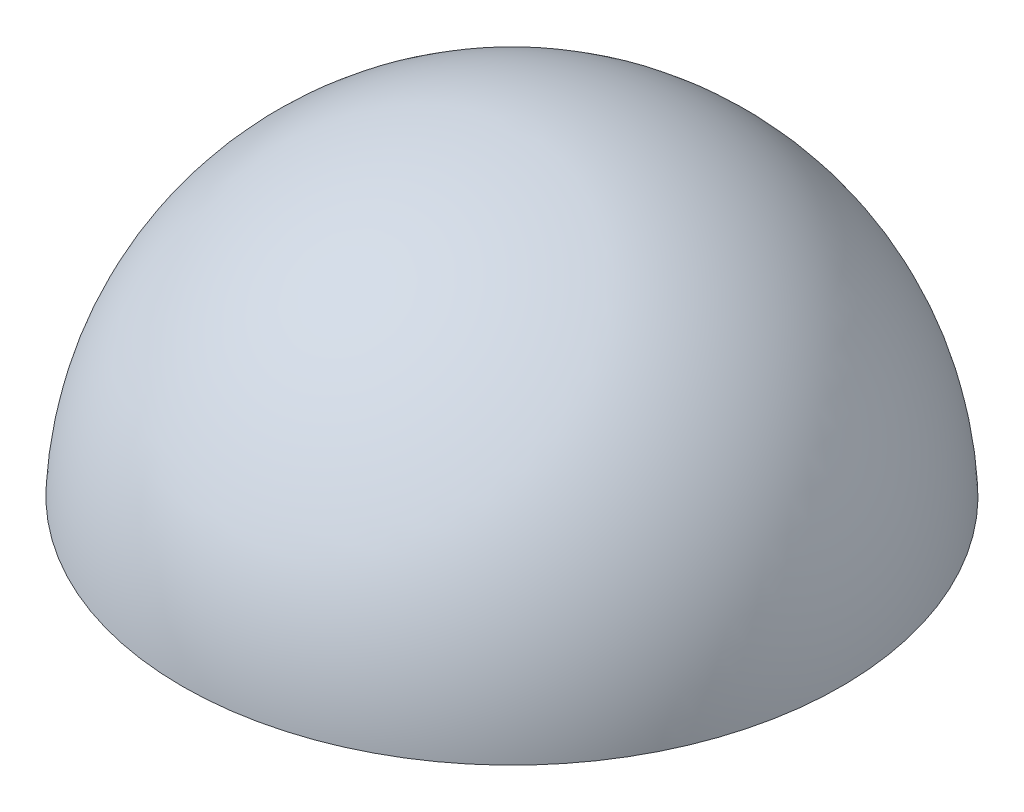
SolidWorks part; units mm, degrees
ref_plane "Front Plane" through (0, 0, 0) normal (0, 0, 1) x (1, 0, 0)
ref_plane "Top Plane" through (0, 0, 0) normal (0, 1, 0) x (1, 0, 0)
ref_plane "Right Plane" through (0, 0, 0) normal (1, 0, 0) x (0, 0, -1)
sketch "Sketch1" plane through (0, 0, 0) normal (0, 1, 0) x (1, 0, 0)
  line L0 (0, -44.45) -> (0, 44.45)
  arc A0 (0, 44.45) -> (0, -44.45) centre (0, 0) ccw
  arc A1 (0, 42.45) -> (0, -42.45) centre (0, 0) ccw
  circle A3 centre (0, 0) radius 44.45 construction
  circle A4 centre (0, 0) radius 42.45 construction
  point P1 (42.45, 0)
  point P6 (42.5077, 12.9959)
  dimension "D1" = 88.9
  dimension "D2" = 2
revolve "Revolve1" add sketch "Sketch1" angle 180 about L0 region at (-43.4561, 0, 0)
sketch "Sketch2" plane through (0, 0, 0) normal (0, 1, 0) x (1, 0, 0)
  circle A0 centre (0, 0) radius 44.45
extrude "Cut-Extrude1" cut sketch "Sketch2" along normal blind 2
sketch "30deg" plane through (0, 0, 0) normal (1, 0, 0) x (0, 0, -1)
  line L0 (0, 0) -> (38.4948, 22.225) construction
  line L1 (0, 0) -> (44.45, 0) construction
  line L7 (0, 0) -> (22.225, 38.4948) construction
  line L8 (0, 0) -> (44.45, 0) construction
  line L10 (0, 0) -> (38.4948, 22.225) construction
  line L25 (0, 0) -> (0, 49000) construction
  dimension "D2" = 3
  dimension "D3" = 30
  dimension "D1" = 44.45
sketch "Sketch4" plane through (0, 0, 0) normal (0, 1, 0) x (1, 0, 0)
  line L0 (0, 0) -> (0, 43.45)
  line L1 (0.5, 44.45) -> (-0.5, 44.45)
  line L2 (-0.5, 43.45) -> (0.5, 43.45)
  line L3 (-0.5, 43.45) -> (-0.5, 44.45)
  line L4 (0.5, 43.45) -> (0.5, 44.45)
  line L5 (0, 0) -> (21.725, 37.6288)
  line L6 (21.292, 37.8788) -> (21.792, 38.7448)
  line L7 (21.292, 37.8788) -> (22.158, 37.3788)
  line L8 (22.158, 37.3788) -> (22.658, 38.2448)
  line L9 (22.658, 38.2448) -> (21.792, 38.7448)
  line L10 (0, 0) -> (37.6288, 21.725)
  line L11 (37.3788, 22.158) -> (38.2448, 22.658)
  line L12 (37.3788, 22.158) -> (37.8788, 21.292)
  line L13 (37.8788, 21.292) -> (38.7448, 21.792)
  line L14 (38.7448, 21.792) -> (38.2448, 22.658)
  line L15 (0, 0) -> (43.45, 0)
  line L16 (43.45, 0.5) -> (44.45, 0.5)
  line L17 (43.45, 0.5) -> (43.45, -0.5)
  line L18 (43.45, -0.5) -> (44.45, -0.5)
  line L19 (44.45, -0.5) -> (44.45, 0.5)
  line L20 (0, 0) -> (37.6288, -21.725)
  line L21 (37.8788, -21.292) -> (38.7448, -21.792)
  line L22 (37.8788, -21.292) -> (37.3788, -22.158)
  line L23 (37.3788, -22.158) -> (38.2448, -22.658)
  line L24 (38.2448, -22.658) -> (38.7448, -21.792)
  line L25 (0, 0) -> (21.725, -37.6288)
  line L26 (22.158, -37.3788) -> (22.658, -38.2448)
  line L27 (22.158, -37.3788) -> (21.292, -37.8788)
  line L28 (21.292, -37.8788) -> (21.792, -38.7448)
  line L29 (21.792, -38.7448) -> (22.658, -38.2448)
  line L30 (0, 0) -> (0, -43.45)
  line L31 (0.5, -43.45) -> (0.5, -44.45)
  line L32 (0.5, -43.45) -> (-0.5, -43.45)
  line L33 (-0.5, -43.45) -> (-0.5, -44.45)
  line L34 (-0.5, -44.45) -> (0.5, -44.45)
  line L35 (0, 0) -> (-21.725, -37.6288)
  line L36 (-21.292, -37.8788) -> (-21.792, -38.7448)
  line L37 (-21.292, -37.8788) -> (-22.158, -37.3788)
  line L38 (-22.158, -37.3788) -> (-22.658, -38.2448)
  line L39 (-22.658, -38.2448) -> (-21.792, -38.7448)
  line L40 (0, 0) -> (-37.6288, -21.725)
  line L41 (-37.3788, -22.158) -> (-38.2448, -22.658)
  line L42 (-37.3788, -22.158) -> (-37.8788, -21.292)
  line L43 (-37.8788, -21.292) -> (-38.7448, -21.792)
  line L44 (-38.7448, -21.792) -> (-38.2448, -22.658)
  line L45 (0, 0) -> (-43.45, 0)
  line L46 (-43.45, -0.5) -> (-44.45, -0.5)
  line L47 (-43.45, -0.5) -> (-43.45, 0.5)
  line L48 (-43.45, 0.5) -> (-44.45, 0.5)
  line L49 (-44.45, 0.5) -> (-44.45, -0.5)
  line L50 (0, 0) -> (-37.6288, 21.725)
  line L51 (-37.8788, 21.292) -> (-38.7448, 21.792)
  line L52 (-37.8788, 21.292) -> (-37.3788, 22.158)
  line L53 (-37.3788, 22.158) -> (-38.2448, 22.658)
  line L54 (-38.2448, 22.658) -> (-38.7448, 21.792)
  line L55 (0, 0) -> (-21.725, 37.6288)
  line L56 (-22.158, 37.3788) -> (-22.658, 38.2448)
  line L57 (-22.158, 37.3788) -> (-21.292, 37.8788)
  line L58 (-21.292, 37.8788) -> (-21.792, 38.7448)
  line L59 (-21.792, 38.7448) -> (-22.658, 38.2448)
  line L60 (0, 0) -> (0, 43.45) construction
  line L61 (0, 0) -> (21.725, 37.6288) construction
  circle A0 centre (0, 0) radius 44.45 construction
  point P7 (0, 44.45)
  point P10 (0, 43.45)
  dimension "D1" = 88.9
  dimension "D2" = 1
  dimension "D3" = 1
  dimension "D5" = 30
  dimension "D4" = 12
ref_plane "Plane1" through (0, 44.45, 0) normal (0, 1, 0) x (1, 0, 0)
sketch "Sketch5" plane through (0, 44.45, 0) normal (0, 1, 0) x (1, 0, 0)
  circle A0 centre (0, 0) radius 0.5
  dimension "D1" = 1
sketch "Sketch6" plane through (0, 0, 0) normal (0, 0, 1) x (1, 0, 0)
  line L0 (44.45, 0) -> (-44.45, 0) construction
  line L1 (-43.45, 0) -> (-44.45, 0) construction
  arc A0 (-44.45, 0) -> (0, 44.45) centre (0, 0) cw
ref_axis "Axis1" through (0, 117.8347, 0) along (0, -1, 0)
sketch "Sketch7" plane through (0, 44.45, 0) normal (0, 1, 0) x (1, 0, 0)
  line L0 (0, 0) -> (0, 88.8986) construction
  line L4 (-0.5, 38.9916) -> (-0.5, 88.8986)
  line L5 (0.5, 38.9916) -> (0.5, 88.8986)
  line L7 (-0.5, 22.7195) -> (-0.5, 37.9915)
  line L9 (0.5, 22.7195) -> (0.5, 37.9915)
  line L10 (0, 0) -> (44.4493, 76.9884) construction
  line L11 (19.0628, 34.0177) -> (44.0163, 77.2384)
  line L12 (19.9288, 33.5177) -> (44.8823, 76.7384)
  line L13 (10.9267, 19.9257) -> (18.5628, 33.1516)
  line L14 (11.7928, 19.4257) -> (19.4288, 32.6516)
  line L17 (0, 0) -> (76.9884, 44.4493) construction
  line L18 (33.5177, 19.9288) -> (76.7384, 44.8823)
  line L19 (34.0177, 19.0628) -> (77.2384, 44.0163)
  line L20 (19.4257, 11.7928) -> (32.6516, 19.4288)
  line L21 (19.9257, 10.9267) -> (33.1516, 18.5628)
  line L24 (0, 0) -> (88.8986, 0) construction
  line L25 (38.9916, 0.5) -> (88.8986, 0.5)
  line L26 (38.9916, -0.5) -> (88.8986, -0.5)
  line L27 (22.7195, 0.5) -> (37.9915, 0.5)
  line L28 (22.7195, -0.5) -> (37.9915, -0.5)
  line L31 (0, 0) -> (76.9884, -44.4493) construction
  line L32 (34.0177, -19.0628) -> (77.2384, -44.0163)
  line L33 (33.5177, -19.9288) -> (76.7384, -44.8823)
  line L34 (19.9257, -10.9267) -> (33.1516, -18.5628)
  line L35 (19.4257, -11.7928) -> (32.6516, -19.4288)
  line L38 (0, 0) -> (44.4493, -76.9884) construction
  line L39 (19.9288, -33.5177) -> (44.8823, -76.7384)
  line L40 (19.0628, -34.0177) -> (44.0163, -77.2384)
  line L41 (11.7928, -19.4257) -> (19.4288, -32.6516)
  line L42 (10.9267, -19.9257) -> (18.5628, -33.1516)
  line L45 (0, 0) -> (0, -88.8986) construction
  line L46 (0.5, -38.9916) -> (0.5, -88.8986)
  line L47 (-0.5, -38.9916) -> (-0.5, -88.8986)
  line L48 (0.5, -22.7195) -> (0.5, -37.9915)
  line L49 (-0.5, -22.7195) -> (-0.5, -37.9915)
  line L52 (0, 0) -> (-44.4493, -76.9884) construction
  line L53 (-19.0628, -34.0177) -> (-44.0163, -77.2384)
  line L54 (-19.9288, -33.5177) -> (-44.8823, -76.7384)
  line L55 (-10.9267, -19.9257) -> (-18.5628, -33.1516)
  line L56 (-11.7928, -19.4257) -> (-19.4288, -32.6516)
  line L59 (0, 0) -> (-76.9884, -44.4493) construction
  line L60 (-33.5177, -19.9288) -> (-76.7384, -44.8823)
  line L61 (-34.0177, -19.0628) -> (-77.2384, -44.0163)
  line L62 (-19.4257, -11.7928) -> (-32.6516, -19.4288)
  line L63 (-19.9257, -10.9267) -> (-33.1516, -18.5628)
  line L66 (0, 0) -> (-88.8986, 0) construction
  line L67 (-38.9916, -0.5) -> (-88.8986, -0.5)
  line L68 (-38.9916, 0.5) -> (-88.8986, 0.5)
  line L69 (-22.7195, -0.5) -> (-37.9915, -0.5)
  line L70 (-22.7195, 0.5) -> (-37.9915, 0.5)
  line L73 (0, 0) -> (-76.9884, 44.4493) construction
  line L74 (-34.0177, 19.0628) -> (-77.2384, 44.0163)
  line L75 (-33.5177, 19.9288) -> (-76.7384, 44.8823)
  line L76 (-19.9257, 10.9267) -> (-33.1516, 18.5628)
  line L77 (-19.4257, 11.7928) -> (-32.6516, 19.4288)
  line L80 (0, 0) -> (-44.4493, 76.9884) construction
  line L81 (-19.9288, 33.5177) -> (-44.8823, 76.7384)
  line L82 (-19.0628, 34.0177) -> (-44.0163, 77.2384)
  line L83 (-11.7928, 19.4257) -> (-19.4288, 32.6516)
  line L84 (-10.9267, 19.9257) -> (-18.5628, 33.1516)
  line L87 (0, 0) -> (0.5, 0) construction
  line L89 (-0.5, 1.866) -> (-0.5, 21.7192)
  line L90 (-0.5, 1.866) -> (-10.4266, 19.0594)
  line L91 (0.5, 1.866) -> (10.4266, 19.0594)
  line L92 (0.5, 1.866) -> (0.5, 21.7192)
  line L93 (1.366, 1.366) -> (18.5594, 11.2926)
  line L94 (1.366, 1.366) -> (11.2926, 18.5594)
  line L95 (1.866, 0.5) -> (21.7192, 0.5)
  line L96 (1.866, 0.5) -> (19.0594, 10.4266)
  line L97 (1.866, -0.5) -> (19.0594, -10.4266)
  line L98 (1.866, -0.5) -> (21.7192, -0.5)
  line L99 (1.366, -1.366) -> (11.2926, -18.5594)
  line L100 (1.366, -1.366) -> (18.5594, -11.2926)
  line L101 (0.5, -1.866) -> (0.5, -21.7192)
  line L102 (0.5, -1.866) -> (10.4266, -19.0594)
  line L103 (-0.5, -1.866) -> (-10.4266, -19.0594)
  line L104 (-0.5, -1.866) -> (-0.5, -21.7192)
  line L105 (-1.366, -1.366) -> (-11.2926, -18.5594)
  line L106 (-1.366, -1.366) -> (-18.5594, -11.2926)
  line L107 (-1.866, -0.5) -> (-21.7192, -0.5)
  line L108 (-1.866, -0.5) -> (-19.0594, -10.4266)
  line L109 (-1.866, 0.5) -> (-19.0594, 10.4266)
  line L110 (-1.866, 0.5) -> (-21.7192, 0.5)
  line L111 (-1.366, 1.366) -> (-11.2926, 18.5594)
  line L112 (-1.366, 1.366) -> (-18.5594, 11.2926)
  circle A0 centre (0, 0) radius 22.225 construction
  circle A1 centre (0, 0) radius 38.4948 construction
  arc A2 (-0.5, 38.9916) -> (-19.0628, 34.0177) centre (0, 0) ccw
  arc A3 (-0.5, 22.7195) -> (-10.9267, 19.9257) centre (0, 0) ccw
  arc A4 (-0.5, 37.9915) -> (-18.5628, 33.1516) centre (0, 0) ccw
  arc A5 (-0.5, 21.7192) -> (-10.4266, 19.0594) centre (0, 0) ccw
  arc A6 (0.5, 88.8986) -> (-0.5, 88.8986) centre (0, 0) ccw
  circle A9 centre (0, 0) radius 88.9 construction
  circle A10 centre (0, 0) radius 38.9948 construction
  circle A11 centre (0, 0) radius 37.9948 construction
  circle A13 centre (0, 0) radius 21.725 construction
  circle A14 centre (0, 0) radius 22.725 construction
  arc A15 (44.8823, 76.7384) -> (44.0163, 77.2384) centre (0, 0) ccw
  arc A16 (77.2384, 44.0163) -> (76.7384, 44.8823) centre (0, 0) ccw
  arc A17 (88.8986, -0.5) -> (88.8986, 0.5) centre (0, 0) ccw
  arc A18 (76.7384, -44.8823) -> (77.2384, -44.0163) centre (0, 0) ccw
  arc A19 (44.0163, -77.2384) -> (44.8823, -76.7384) centre (0, 0) ccw
  arc A20 (-0.5, -88.8986) -> (0.5, -88.8986) centre (0, 0) ccw
  arc A21 (-44.8823, -76.7384) -> (-44.0163, -77.2384) centre (0, 0) ccw
  arc A22 (-77.2384, -44.0163) -> (-76.7384, -44.8823) centre (0, 0) ccw
  arc A23 (-88.8986, 0.5) -> (-88.8986, -0.5) centre (0, 0) ccw
  arc A24 (-76.7384, 44.8823) -> (-77.2384, 44.0163) centre (0, 0) ccw
  arc A25 (-44.0163, 77.2384) -> (-44.8823, 76.7384) centre (0, 0) ccw
  arc A26 (-34.0177, 19.0628) -> (-38.9916, 0.5) centre (0, 0) ccw
  arc A27 (-33.1516, 18.5628) -> (-37.9915, 0.5) centre (0, 0) ccw
  arc A28 (-19.9288, 33.5177) -> (-33.5177, 19.9288) centre (0, 0) ccw
  arc A29 (-19.4288, 32.6516) -> (-32.6516, 19.4288) centre (0, 0) ccw
  arc A30 (19.0628, 34.0177) -> (0.5, 38.9916) centre (0, 0) ccw
  arc A31 (18.5628, 33.1516) -> (0.5, 37.9915) centre (0, 0) ccw
  arc A32 (32.6516, 19.4288) -> (19.4288, 32.6516) centre (0, 0) ccw
  arc A33 (33.5177, 19.9288) -> (19.9288, 33.5177) centre (0, 0) ccw
  arc A34 (37.9915, 0.5) -> (33.1516, 18.5628) centre (0, 0) ccw
  arc A35 (38.9916, 0.5) -> (34.0177, 19.0628) centre (0, 0) ccw
  arc A36 (33.1516, -18.5628) -> (37.9915, -0.5) centre (0, 0) ccw
  arc A37 (34.0177, -19.0628) -> (38.9916, -0.5) centre (0, 0) ccw
  arc A38 (19.4288, -32.6516) -> (32.6516, -19.4288) centre (0, 0) ccw
  arc A39 (19.9288, -33.5177) -> (33.5177, -19.9288) centre (0, 0) ccw
  arc A40 (0.5, -37.9915) -> (18.5628, -33.1516) centre (0, 0) ccw
  arc A41 (0.5, -38.9916) -> (19.0628, -34.0177) centre (0, 0) ccw
  arc A42 (-18.5628, -33.1516) -> (-0.5, -37.9915) centre (0, 0) ccw
  arc A43 (-19.0628, -34.0177) -> (-0.5, -38.9916) centre (0, 0) ccw
  arc A44 (-33.5177, -19.9288) -> (-19.9288, -33.5177) centre (0, 0) ccw
  arc A45 (-32.6516, -19.4288) -> (-19.4288, -32.6516) centre (0, 0) ccw
  arc A46 (-38.9916, -0.5) -> (-34.0177, -19.0628) centre (0, 0) ccw
  arc A47 (-37.9915, -0.5) -> (-33.1516, -18.5628) centre (0, 0) ccw
  arc A48 (-11.7928, 19.4257) -> (-19.4257, 11.7928) centre (0, 0) ccw
  arc A49 (-11.2926, 18.5594) -> (-18.5594, 11.2926) centre (0, 0) ccw
  arc A50 (-19.9257, 10.9267) -> (-22.7195, 0.5) centre (0, 0) ccw
  arc A51 (-19.0594, 10.4266) -> (-21.7192, 0.5) centre (0, 0) ccw
  arc A52 (-21.7192, -0.5) -> (-19.0594, -10.4266) centre (0, 0) ccw
  arc A53 (-22.7195, -0.5) -> (-19.9257, -10.9267) centre (0, 0) ccw
  arc A54 (10.4266, 19.0594) -> (0.5, 21.7192) centre (0, 0) ccw
  arc A55 (10.9267, 19.9257) -> (0.5, 22.7195) centre (0, 0) ccw
  arc A56 (18.5594, 11.2926) -> (11.2926, 18.5594) centre (0, 0) ccw
  arc A57 (19.4257, 11.7928) -> (11.7928, 19.4257) centre (0, 0) ccw
  arc A58 (21.7192, 0.5) -> (19.0594, 10.4266) centre (0, 0) ccw
  arc A59 (22.7195, 0.5) -> (19.9257, 10.9267) centre (0, 0) ccw
  arc A60 (19.9257, -10.9267) -> (22.7195, -0.5) centre (0, 0) ccw
  arc A61 (19.0594, -10.4266) -> (21.7192, -0.5) centre (0, 0) ccw
  arc A62 (11.2926, -18.5594) -> (18.5594, -11.2926) centre (0, 0) ccw
  arc A63 (11.7928, -19.4257) -> (19.4257, -11.7928) centre (0, 0) ccw
  arc A64 (0.5, -22.7195) -> (10.9267, -19.9257) centre (0, 0) ccw
  arc A65 (0.5, -21.7192) -> (10.4266, -19.0594) centre (0, 0) ccw
  arc A66 (-10.4266, -19.0594) -> (-0.5, -21.7192) centre (0, 0) ccw
  arc A67 (-10.9267, -19.9257) -> (-0.5, -22.7195) centre (0, 0) ccw
  arc A68 (-19.4257, -11.7928) -> (-11.7928, -19.4257) centre (0, 0) ccw
  arc A69 (-18.5594, -11.2926) -> (-11.2926, -18.5594) centre (0, 0) ccw
  point P11 (21.725, 0)
  point P13 (22.725, 0)
  point P17 (0.5, 0)
  point P19 (-0.5, 0)
  point P27 (38.9948, 0)
  point P30 (37.9948, 0)
  point P114 (-1.366, 1.366)
  dimension "D5" = 177.8
  dimension "D1" = 0.5
  dimension "D2" = 0.5
  dimension "D6" = 12
sketch "Sketch9" plane through (0, 44.45, 0) normal (0, 1, 0) x (1, 0, 0)
  line L0 (0, 0) -> (0, -88.9)
  circle A0 centre (0, 0) radius 22.225
  circle A1 centre (0, 0) radius 38.4948
  circle A2 centre (0, 0) radius 88.9
  circle A3 centre (0, 0) radius 38.4948 construction
  circle A4 centre (0, 0) radius 22.225 construction
  dimension "D1" = 177.8
sketch "Sketch10" plane through (0, 44.45, 0) normal (0, 1, 0) x (1, 0, 0)
  line L0 (88.9, 0) -> (-88.9, 0) construction
  line L1 (0, 88.9) -> (0, -88.9) construction
  line L2 (-29.64, 88.9) -> (-29.64, -88.9) construction
  line L3 (-59.28, 88.9) -> (-59.28, -88.9) construction
  line L4 (-88.92, 88.9) -> (-88.92, -88.9) construction
  line L5 (29.64, 88.9) -> (29.64, -88.9) construction
  line L6 (59.28, 88.9) -> (59.28, -88.9) construction
  line L7 (88.92, 88.9) -> (88.92, -88.9) construction
  line L8 (-89.42, 88.9) -> (-89.42, -88.9)
  line L9 (-59.78, 88.9) -> (-59.78, 0.5)
  line L10 (-30.14, 88.9) -> (-30.14, 0.5)
  line L11 (-0.5, 88.9) -> (-0.5, 0.5)
  line L12 (29.14, 88.9) -> (29.14, 0.5)
  line L13 (58.78, 88.9) -> (58.78, 0.5)
  line L14 (88.42, 88.9) -> (88.42, 0.5)
  line L15 (-88.42, 88.9) -> (-88.42, 0.5)
  line L16 (-58.78, 88.9) -> (-58.78, 0.5)
  line L17 (-29.14, 88.9) -> (-29.14, 0.5)
  line L18 (0.5, 88.9) -> (0.5, 0.5)
  line L19 (30.14, 88.9) -> (30.14, 0.5)
  line L20 (59.78, 88.9) -> (59.78, 0.5)
  line L21 (89.42, 88.9) -> (89.42, -88.9)
  line L22 (88.42, 0.5) -> (59.78, 0.5)
  line L23 (88.42, -0.5) -> (59.78, -0.5)
  line L24 (-88.42, -0.5) -> (-88.42, -88.9)
  line L25 (88.9, 0.5) -> (-88.9, 0.5) construction
  line L26 (88.9, -0.5) -> (-88.9, -0.5) construction
  line L27 (-59.78, 0.5) -> (-88.42, 0.5)
  line L28 (-88.42, 88.9) -> (-88.42, -88.9) construction
  line L29 (-59.78, -0.5) -> (-88.42, -0.5)
  line L30 (-59.78, -0.5) -> (-59.78, -88.9)
  line L31 (-58.78, -0.5) -> (-58.78, -88.9)
  line L32 (-59.78, 88.9) -> (-59.78, -88.9) construction
  line L33 (-30.14, -0.5) -> (-30.14, -88.9)
  line L34 (-58.78, 88.9) -> (-58.78, -88.9) construction
  line L35 (-30.14, 88.9) -> (-30.14, -88.9) construction
  line L36 (-29.14, -0.5) -> (-29.14, -88.9)
  line L37 (-29.14, 88.9) -> (-29.14, -88.9) construction
  line L38 (-0.5, -0.5) -> (-0.5, -88.9)
  line L39 (-0.5, 88.9) -> (-0.5, -88.9) construction
  line L40 (0.5, -0.5) -> (0.5, -88.9)
  line L41 (0.5, 88.9) -> (0.5, -88.9) construction
  line L42 (29.14, -0.5) -> (29.14, -88.9)
  line L43 (29.14, 88.9) -> (29.14, -88.9) construction
  line L44 (30.14, -0.5) -> (30.14, -88.9)
  line L45 (30.14, 88.9) -> (30.14, -88.9) construction
  line L46 (58.78, -0.5) -> (58.78, -88.9)
  line L47 (58.78, 88.9) -> (58.78, -88.9) construction
  line L48 (59.78, -0.5) -> (59.78, -88.9)
  line L49 (59.78, 88.9) -> (59.78, -88.9) construction
  line L50 (88.42, -0.5) -> (88.42, -88.9)
  line L51 (88.42, 88.9) -> (88.42, -88.9) construction
  line L52 (58.78, 0.5) -> (30.14, 0.5)
  line L53 (58.78, -0.5) -> (30.14, -0.5)
  line L54 (-30.14, 0.5) -> (-58.78, 0.5)
  line L55 (-30.14, -0.5) -> (-58.78, -0.5)
  line L56 (-0.5, 0.5) -> (-29.14, 0.5)
  line L57 (-0.5, -0.5) -> (-29.14, -0.5)
  line L58 (29.14, 0.5) -> (0.5, 0.5)
  line L59 (29.14, -0.5) -> (0.5, -0.5)
  arc A0 (-89.42, 88.9) -> (-88.42, 88.9) centre (-88.92, 88.9) cw
  arc A1 (-89.42, -88.9) -> (-88.42, -88.9) centre (-88.92, -88.9) ccw
  arc A2 (-59.78, 88.9) -> (-58.78, 88.9) centre (-59.28, 88.9) cw
  arc A3 (-59.78, -88.9) -> (-58.78, -88.9) centre (-59.28, -88.9) ccw
  arc A4 (-30.14, 88.9) -> (-29.14, 88.9) centre (-29.64, 88.9) cw
  arc A5 (-30.14, -88.9) -> (-29.14, -88.9) centre (-29.64, -88.9) ccw
  arc A6 (-0.5, 88.9) -> (0.5, 88.9) centre (0, 88.9) cw
  arc A7 (-0.5, -88.9) -> (0.5, -88.9) centre (0, -88.9) ccw
  arc A8 (29.14, 88.9) -> (30.14, 88.9) centre (29.64, 88.9) cw
  arc A9 (29.14, -88.9) -> (30.14, -88.9) centre (29.64, -88.9) ccw
  arc A10 (58.78, 88.9) -> (59.78, 88.9) centre (59.28, 88.9) cw
  arc A11 (58.78, -88.9) -> (59.78, -88.9) centre (59.28, -88.9) ccw
  arc A12 (88.42, 88.9) -> (89.42, 88.9) centre (88.92, 88.9) cw
  arc A13 (88.42, -88.9) -> (89.42, -88.9) centre (88.92, -88.9) ccw
  arc A15 (-88.9, 0.5) -> (-88.92, 0.4996) centre (-88.9, 0) ccw
  arc A16 (-88.92, -0.4996) -> (-88.9, -0.5) centre (-88.9, 0) ccw
  point P4 (0, 0)
  point P8 (0, 0)
  dimension "D1" = 177.8
  dimension "D3" = 0.5
  dimension "D4" = 0.5
  dimension "D5" = 0.5
  dimension "D6" = 0.5
  dimension "D2" = 4
sketch "Sketch13" plane through (0, 44.45, 0) normal (0, 1, 0) x (1, 0, 0)
  line L0 (0, -11.5265) -> (0, 11.5265) construction
  line L1 (-11.5265, 0) -> (11.5265, 0) construction
  line L2 (-11.5265, -0.5) -> (-0.5, -0.5)
  line L3 (-18.1069, 3.2902) -> (-11.5265, 3.2902) construction
  line L4 (-18.1069, 3.2902) -> (-18.1069, -3.2902) construction
  line L5 (-18.1069, -3.2902) -> (-11.5265, -3.2902) construction
  line L6 (-11.5265, 3.2902) -> (-11.5265, -3.2902) construction
  line L7 (-3.2902, 18.1069) -> (3.2902, 18.1069) construction
  line L8 (-3.2902, 18.1069) -> (-3.2902, 11.5265) construction
  line L9 (-3.2902, 11.5265) -> (3.2902, 11.5265) construction
  line L10 (3.2902, 18.1069) -> (3.2902, 11.5265) construction
  line L11 (0.5, -11.5265) -> (0.5, -0.5)
  line L12 (-11.5265, 0.5) -> (-0.5, 0.5)
  line L13 (-0.5, -11.5265) -> (-0.5, -0.5)
  line L14 (-0.5, 0.5) -> (-0.5, 11.5265)
  line L15 (0.5, 0.5) -> (0.5, 11.5265)
  line L16 (-0.5, -11.5265) -> (-0.5, 11.5265) construction
  line L17 (0.5, 0.5) -> (11.5265, 0.5)
  line L18 (0.5, -11.5265) -> (0.5, 11.5265) construction
  line L19 (0.5, -0.5) -> (11.5265, -0.5)
  line L20 (-11.5265, 0.5) -> (11.5265, 0.5) construction
  line L21 (-11.5265, 0.5) -> (-11.5265, -0.5)
  line L22 (-11.5265, -0.5) -> (11.5265, -0.5) construction
  line L23 (11.5265, 0.5) -> (11.5265, -0.5)
  line L24 (-0.5, -11.5265) -> (0.5, -11.5265)
  line L25 (-0.5, 11.5265) -> (0.5, 11.5265)
  line L26 (18.1035, -0.5) -> (29.13, -0.5)
  line L27 (30.13, -11.5265) -> (30.13, -0.5)
  line L28 (18.1035, 0.5) -> (29.13, 0.5)
  line L29 (29.13, -11.5265) -> (29.13, -0.5)
  line L30 (29.13, 0.5) -> (29.13, 11.5265)
  line L31 (30.13, 0.5) -> (30.13, 11.5265)
  line L32 (30.13, 0.5) -> (41.1565, 0.5)
  line L33 (30.13, -0.5) -> (41.1565, -0.5)
  line L34 (18.1035, 0.5) -> (18.1035, -0.5)
  line L35 (41.1565, 0.5) -> (41.1565, -0.5)
  line L36 (29.13, -11.5265) -> (30.13, -11.5265)
  line L37 (29.13, 11.5265) -> (30.13, 11.5265)
  line L38 (29.63, -11.5265) -> (29.63, 11.5265) construction
  line L39 (18.1035, 0) -> (41.1565, 0) construction
  line L40 (11.5231, 3.2902) -> (18.1035, 3.2902) construction
  line L41 (11.5231, 3.2902) -> (11.5231, -3.2902) construction
  line L42 (11.5231, -3.2902) -> (18.1035, -3.2902) construction
  line L43 (18.1035, 3.2902) -> (18.1035, -3.2902) construction
  line L44 (26.3398, 18.1069) -> (32.9202, 18.1069) construction
  line L45 (26.3398, 18.1069) -> (26.3398, 11.5265) construction
  line L46 (26.3398, 11.5265) -> (32.9202, 11.5265) construction
  line L47 (32.9202, 18.1069) -> (32.9202, 11.5265) construction
  line L48 (47.7335, -0.5) -> (58.76, -0.5)
  line L49 (59.76, -11.5265) -> (59.76, -0.5)
  line L50 (47.7335, 0.5) -> (58.76, 0.5)
  line L51 (58.76, -11.5265) -> (58.76, -0.5)
  line L52 (58.76, 0.5) -> (58.76, 11.5265)
  line L53 (59.76, 0.5) -> (59.76, 11.5265)
  line L54 (59.76, 0.5) -> (70.7865, 0.5)
  line L55 (59.76, -0.5) -> (70.7865, -0.5)
  line L56 (47.7335, 0.5) -> (47.7335, -0.5)
  line L57 (70.7865, 0.5) -> (70.7865, -0.5)
  line L58 (58.76, -11.5265) -> (59.76, -11.5265)
  line L59 (58.76, 11.5265) -> (59.76, 11.5265)
  line L60 (59.26, -11.5265) -> (59.26, 11.5265) construction
  line L61 (47.7335, 0) -> (70.7865, 0) construction
  line L62 (41.1531, 3.2902) -> (47.7335, 3.2902) construction
  line L63 (41.1531, 3.2902) -> (41.1531, -3.2902) construction
  line L64 (41.1531, -3.2902) -> (47.7335, -3.2902) construction
  line L65 (47.7335, 3.2902) -> (47.7335, -3.2902) construction
  line L66 (55.9698, 18.1069) -> (62.5502, 18.1069) construction
  line L67 (55.9698, 18.1069) -> (55.9698, 11.5265) construction
  line L68 (55.9698, 11.5265) -> (62.5502, 11.5265) construction
  line L69 (62.5502, 18.1069) -> (62.5502, 11.5265) construction
  line L70 (-11.5265, 29.13) -> (-0.5, 29.13)
  line L71 (0.5, 18.1035) -> (0.5, 29.13)
  line L72 (-11.5265, 30.13) -> (-0.5, 30.13)
  line L73 (-0.5, 18.1035) -> (-0.5, 29.13)
  line L74 (-0.5, 30.13) -> (-0.5, 41.1565)
  line L75 (0.5, 30.13) -> (0.5, 41.1565)
  line L76 (0.5, 30.13) -> (11.5265, 30.13)
  line L77 (0.5, 29.13) -> (11.5265, 29.13)
  line L78 (-11.5265, 30.13) -> (-11.5265, 29.13)
  line L79 (11.5265, 30.13) -> (11.5265, 29.13)
  line L80 (-0.5, 18.1035) -> (0.5, 18.1035)
  line L81 (-0.5, 41.1565) -> (0.5, 41.1565)
  line L82 (18.1035, 29.13) -> (29.13, 29.13)
  line L83 (30.13, 18.1035) -> (30.13, 29.13)
  line L84 (18.1035, 30.13) -> (29.13, 30.13)
  line L85 (29.13, 18.1035) -> (29.13, 29.13)
  line L86 (29.13, 30.13) -> (29.13, 41.1565)
  line L87 (30.13, 30.13) -> (30.13, 41.1565)
  line L88 (30.13, 30.13) -> (41.1565, 30.13)
  line L89 (30.13, 29.13) -> (41.1565, 29.13)
  line L90 (18.1035, 30.13) -> (18.1035, 29.13)
  line L91 (41.1565, 30.13) -> (41.1565, 29.13)
  line L92 (29.13, 18.1035) -> (30.13, 18.1035)
  line L93 (29.13, 41.1565) -> (30.13, 41.1565)
  line L94 (47.7335, 29.13) -> (58.76, 29.13)
  line L95 (59.76, 18.1035) -> (59.76, 29.13)
  line L96 (47.7335, 30.13) -> (58.76, 30.13)
  line L97 (58.76, 18.1035) -> (58.76, 29.13)
  line L98 (58.76, 30.13) -> (58.76, 41.1565)
  line L99 (59.76, 30.13) -> (59.76, 41.1565)
  line L100 (59.76, 30.13) -> (70.7865, 30.13)
  line L101 (59.76, 29.13) -> (70.7865, 29.13)
  line L102 (47.7335, 30.13) -> (47.7335, 29.13)
  line L103 (70.7865, 30.13) -> (70.7865, 29.13)
  line L104 (58.76, 18.1035) -> (59.76, 18.1035)
  line L105 (58.76, 41.1565) -> (59.76, 41.1565)
  line L106 (0, 18.1035) -> (0, 41.1565) construction
  line L107 (-11.5265, 29.63) -> (11.5265, 29.63) construction
  line L108 (-18.1069, 32.9202) -> (-11.5265, 32.9202) construction
  line L109 (-18.1069, 32.9202) -> (-18.1069, 26.3398) construction
  line L110 (-18.1069, 26.3398) -> (-11.5265, 26.3398) construction
  line L111 (-11.5265, 32.9202) -> (-11.5265, 26.3398) construction
  line L112 (-3.2902, 47.7369) -> (3.2902, 47.7369) construction
  line L113 (-3.2902, 47.7369) -> (-3.2902, 41.1565) construction
  line L114 (-3.2902, 41.1565) -> (3.2902, 41.1565) construction
  line L115 (3.2902, 47.7369) -> (3.2902, 41.1565) construction
  line L116 (29.63, 18.1035) -> (29.63, 41.1565) construction
  line L117 (18.1035, 29.63) -> (41.1565, 29.63) construction
  line L118 (11.5231, 32.9202) -> (18.1035, 32.9202) construction
  line L119 (11.5231, 32.9202) -> (11.5231, 26.3398) construction
  line L120 (11.5231, 26.3398) -> (18.1035, 26.3398) construction
  line L121 (18.1035, 32.9202) -> (18.1035, 26.3398) construction
  line L122 (26.3398, 47.7369) -> (32.9202, 47.7369) construction
  line L123 (26.3398, 47.7369) -> (26.3398, 41.1565) construction
  line L124 (26.3398, 41.1565) -> (32.9202, 41.1565) construction
  line L125 (32.9202, 47.7369) -> (32.9202, 41.1565) construction
  line L126 (59.26, 18.1035) -> (59.26, 41.1565) construction
  line L127 (47.7335, 29.63) -> (70.7865, 29.63) construction
  line L128 (41.1531, 32.9202) -> (47.7335, 32.9202) construction
  line L129 (41.1531, 32.9202) -> (41.1531, 26.3398) construction
  line L130 (41.1531, 26.3398) -> (47.7335, 26.3398) construction
  line L131 (47.7335, 32.9202) -> (47.7335, 26.3398) construction
  line L132 (55.9698, 47.7369) -> (62.5502, 47.7369) construction
  line L133 (55.9698, 47.7369) -> (55.9698, 41.1565) construction
  line L134 (55.9698, 41.1565) -> (62.5502, 41.1565) construction
  line L135 (62.5502, 47.7369) -> (62.5502, 41.1565) construction
  line L136 (-11.5265, 58.76) -> (-0.5, 58.76)
  line L137 (0.5, 47.7335) -> (0.5, 58.76)
  line L138 (-11.5265, 59.76) -> (-0.5, 59.76)
  line L139 (-0.5, 47.7335) -> (-0.5, 58.76)
  line L140 (-0.5, 59.76) -> (-0.5, 70.7865)
  line L141 (0.5, 59.76) -> (0.5, 70.7865)
  line L142 (0.5, 59.76) -> (11.5265, 59.76)
  line L143 (0.5, 58.76) -> (11.5265, 58.76)
  line L144 (-11.5265, 59.76) -> (-11.5265, 58.76)
  line L145 (11.5265, 59.76) -> (11.5265, 58.76)
  line L146 (-0.5, 47.7335) -> (0.5, 47.7335)
  line L147 (-0.5, 70.7865) -> (0.5, 70.7865)
  line L148 (18.1035, 58.76) -> (29.13, 58.76)
  line L149 (30.13, 47.7335) -> (30.13, 58.76)
  line L150 (18.1035, 59.76) -> (29.13, 59.76)
  line L151 (29.13, 47.7335) -> (29.13, 58.76)
  line L152 (29.13, 59.76) -> (29.13, 70.7865)
  line L153 (30.13, 59.76) -> (30.13, 70.7865)
  line L154 (30.13, 59.76) -> (41.1565, 59.76)
  line L155 (30.13, 58.76) -> (41.1565, 58.76)
  line L156 (18.1035, 59.76) -> (18.1035, 58.76)
  line L157 (41.1565, 59.76) -> (41.1565, 58.76)
  line L158 (29.13, 47.7335) -> (30.13, 47.7335)
  line L159 (29.13, 70.7865) -> (30.13, 70.7865)
  line L160 (47.7335, 58.76) -> (58.76, 58.76)
  line L161 (59.76, 47.7335) -> (59.76, 58.76)
  line L162 (47.7335, 59.76) -> (58.76, 59.76)
  line L163 (58.76, 47.7335) -> (58.76, 58.76)
  line L164 (58.76, 59.76) -> (58.76, 70.7865)
  line L165 (59.76, 59.76) -> (59.76, 70.7865)
  line L166 (59.76, 59.76) -> (70.7865, 59.76)
  line L167 (59.76, 58.76) -> (70.7865, 58.76)
  line L168 (47.7335, 59.76) -> (47.7335, 58.76)
  line L169 (70.7865, 59.76) -> (70.7865, 58.76)
  line L170 (58.76, 47.7335) -> (59.76, 47.7335)
  line L171 (58.76, 70.7865) -> (59.76, 70.7865)
  line L172 (0, 47.7335) -> (0, 70.7865) construction
  line L173 (-11.5265, 59.26) -> (11.5265, 59.26) construction
  line L174 (-18.1069, 62.5502) -> (-11.5265, 62.5502) construction
  line L175 (-18.1069, 62.5502) -> (-18.1069, 55.9698) construction
  line L176 (-18.1069, 55.9698) -> (-11.5265, 55.9698) construction
  line L177 (-11.5265, 62.5502) -> (-11.5265, 55.9698) construction
  line L178 (-3.2902, 77.3669) -> (3.2902, 77.3669) construction
  line L179 (-3.2902, 77.3669) -> (-3.2902, 70.7865) construction
  line L180 (-3.2902, 70.7865) -> (3.2902, 70.7865) construction
  line L181 (3.2902, 77.3669) -> (3.2902, 70.7865) construction
  line L182 (29.63, 47.7335) -> (29.63, 70.7865) construction
  line L183 (18.1035, 59.26) -> (41.1565, 59.26) construction
  line L184 (11.5231, 62.5502) -> (18.1035, 62.5502) construction
  line L185 (11.5231, 62.5502) -> (11.5231, 55.9698) construction
  line L186 (11.5231, 55.9698) -> (18.1035, 55.9698) construction
  line L187 (18.1035, 62.5502) -> (18.1035, 55.9698) construction
  line L188 (26.3398, 77.3669) -> (32.9202, 77.3669) construction
  line L189 (26.3398, 77.3669) -> (26.3398, 70.7865) construction
  line L190 (26.3398, 70.7865) -> (32.9202, 70.7865) construction
  line L191 (32.9202, 77.3669) -> (32.9202, 70.7865) construction
  line L192 (59.26, 47.7335) -> (59.26, 70.7865) construction
  line L193 (47.7335, 59.26) -> (70.7865, 59.26) construction
  line L194 (41.1531, 62.5502) -> (47.7335, 62.5502) construction
  line L195 (41.1531, 62.5502) -> (41.1531, 55.9698) construction
  line L196 (41.1531, 55.9698) -> (47.7335, 55.9698) construction
  line L197 (47.7335, 62.5502) -> (47.7335, 55.9698) construction
  line L198 (55.9698, 77.3669) -> (62.5502, 77.3669) construction
  line L199 (55.9698, 77.3669) -> (55.9698, 70.7865) construction
  line L200 (55.9698, 70.7865) -> (62.5502, 70.7865) construction
  line L201 (62.5502, 77.3669) -> (62.5502, 70.7865) construction
  circle A0 centre (0, 0) radius 88.9 construction
  point P4 (0, 0)
  point P8 (0, 0)
  point P12 (-11.5265, 0)
  point P35 (29.63, 0)
  point P38 (29.63, 0)
  point P61 (59.26, 0)
  point P64 (59.26, 0)
  point P86 (0, 29.63)
  point P89 (0, 29.63)
  point P112 (29.63, 29.63)
  point P115 (29.63, 29.63)
  point P138 (59.26, 29.63)
  point P141 (59.26, 29.63)
  point P164 (0, 59.26)
  point P167 (0, 59.26)
  point P190 (29.63, 59.26)
  point P193 (29.63, 59.26)
  point P216 (59.26, 59.26)
  point P219 (59.26, 59.26)
  dimension "D1" = 177.8
  dimension "D2" = 29.6333
  dimension "D3" = 0.5
  dimension "D4" = 0.5
  dimension "D5" = 3
  dimension "D6" = 3
sketch "Sketch14" plane through (0, 44.45, 0) normal (0, 1, 0) x (1, 0, 0)
  line L0 (93.6145, -50.5339) -> (93.6145, -58.1871) construction
  line L13 (97.4411, -54.3605) -> (89.7879, -54.3605) construction
  line L14 (97.4411, -53.8605) -> (94.1145, -53.8605)
  line L15 (82.6245, -56.0696) -> (89.7879, -56.0696) construction
  line L16 (82.6245, -56.0696) -> (82.6245, -52.6514) construction
  line L17 (82.6245, -52.6514) -> (89.7879, -52.6514) construction
  line L18 (89.7879, -56.0696) -> (89.7879, -52.6514) construction
  line L19 (97.4411, -39.0405) -> (94.1145, -39.0405)
  line L20 (93.1145, -35.7139) -> (93.1145, -39.0405)
  line L21 (90.0328, -47.0776) -> (97.1962, -47.0776) construction
  line L22 (90.0328, -47.0776) -> (90.0328, -49.3704) construction
  line L23 (90.0328, -49.3704) -> (97.1962, -49.3704) construction
  line L24 (97.1962, -47.0776) -> (97.1962, -49.3704) construction
  line L25 (97.4411, -40.0405) -> (94.1145, -40.0405)
  line L26 (94.1145, -35.7139) -> (94.1145, -39.0405)
  line L27 (93.1145, -50.5339) -> (93.1145, -53.8605)
  line L28 (97.4411, -54.8605) -> (94.1145, -54.8605)
  line L29 (94.1145, -50.5339) -> (94.1145, -53.8605)
  line L30 (97.4411, -53.8605) -> (97.4411, -54.8605)
  line L31 (89.7879, -53.8605) -> (89.7879, -54.8605)
  line L32 (93.1145, -50.5339) -> (94.1145, -50.5339)
  line L33 (93.1145, -58.1871) -> (94.1145, -58.1871)
  line L34 (93.1145, -54.8605) -> (93.1145, -58.1871)
  line L35 (93.1145, -54.8605) -> (89.7879, -54.8605)
  line L36 (93.1145, -50.5339) -> (93.1145, -58.1871) construction
  line L37 (94.1145, -54.8605) -> (94.1145, -58.1871)
  line L38 (97.4411, -54.8605) -> (89.7879, -54.8605) construction
  line L39 (93.1145, -53.8605) -> (89.7879, -53.8605)
  line L40 (94.1145, -50.5339) -> (94.1145, -58.1871) construction
  line L41 (97.4411, -39.0405) -> (97.4411, -40.0405)
  line L42 (97.4411, -53.8605) -> (89.7879, -53.8605) construction
  line L43 (89.7879, -39.0405) -> (89.7879, -40.0405)
  line L44 (93.1145, -35.7139) -> (94.1145, -35.7139)
  line L45 (93.1145, -43.3671) -> (94.1145, -43.3671)
  line L46 (93.1145, -40.0405) -> (93.1145, -43.3671)
  line L47 (93.1145, -40.0405) -> (89.7879, -40.0405)
  line L48 (94.1145, -40.0405) -> (94.1145, -43.3671)
  line L49 (93.1145, -39.0405) -> (89.7879, -39.0405)
  line L50 (93.6145, -35.7139) -> (93.6145, -43.3671) construction
  line L51 (97.4411, -39.5405) -> (89.7879, -39.5405) construction
  line L52 (82.6245, -41.2496) -> (89.7879, -41.2496) construction
  line L53 (82.6245, -41.2496) -> (82.6245, -37.8314) construction
  line L54 (82.6245, -37.8314) -> (89.7879, -37.8314) construction
  line L55 (89.7879, -41.2496) -> (89.7879, -37.8314) construction
  line L56 (90.0328, -32.2576) -> (97.1962, -32.2576) construction
  line L57 (90.0328, -32.2576) -> (90.0328, -34.5504) construction
  line L58 (90.0328, -34.5504) -> (97.1962, -34.5504) construction
  line L59 (97.1962, -32.2576) -> (97.1962, -34.5504) construction
  line L60 (97.4411, -24.2205) -> (94.1145, -24.2205)
  line L61 (93.1145, -20.8939) -> (93.1145, -24.2205)
  line L62 (97.4411, -25.2205) -> (94.1145, -25.2205)
  line L63 (94.1145, -20.8939) -> (94.1145, -24.2205)
  line L64 (97.4411, -24.2205) -> (97.4411, -25.2205)
  line L65 (89.7879, -24.2205) -> (89.7879, -25.2205)
  line L66 (93.1145, -20.8939) -> (94.1145, -20.8939)
  line L67 (93.1145, -28.5471) -> (94.1145, -28.5471)
  line L68 (93.1145, -25.2205) -> (93.1145, -28.5471)
  line L69 (93.1145, -25.2205) -> (89.7879, -25.2205)
  line L70 (94.1145, -25.2205) -> (94.1145, -28.5471)
  line L71 (93.1145, -24.2205) -> (89.7879, -24.2205)
  line L72 (93.6145, -20.8939) -> (93.6145, -28.5471) construction
  line L73 (97.4411, -24.7205) -> (89.7879, -24.7205) construction
  line L74 (82.6245, -26.4296) -> (89.7879, -26.4296) construction
  line L75 (82.6245, -26.4296) -> (82.6245, -23.0114) construction
  line L76 (82.6245, -23.0114) -> (89.7879, -23.0114) construction
  line L77 (89.7879, -26.4296) -> (89.7879, -23.0114) construction
  line L78 (90.0328, -17.4376) -> (97.1962, -17.4376) construction
  line L79 (90.0328, -17.4376) -> (90.0328, -19.7304) construction
  line L80 (90.0328, -19.7304) -> (97.1962, -19.7304) construction
  line L81 (97.1962, -17.4376) -> (97.1962, -19.7304) construction
  line L82 (97.4411, -9.4005) -> (94.1145, -9.4005)
  line L83 (93.1145, -6.0739) -> (93.1145, -9.4005)
  line L84 (97.4411, -10.4005) -> (94.1145, -10.4005)
  line L85 (94.1145, -6.0739) -> (94.1145, -9.4005)
  line L86 (97.4411, -9.4005) -> (97.4411, -10.4005)
  line L87 (89.7879, -9.4005) -> (89.7879, -10.4005)
  line L88 (93.1145, -6.0739) -> (94.1145, -6.0739)
  line L89 (93.1145, -13.7271) -> (94.1145, -13.7271)
  line L90 (93.1145, -10.4005) -> (93.1145, -13.7271)
  line L91 (93.1145, -10.4005) -> (89.7879, -10.4005)
  line L92 (94.1145, -10.4005) -> (94.1145, -13.7271)
  line L93 (93.1145, -9.4005) -> (89.7879, -9.4005)
  line L94 (93.6145, -6.0739) -> (93.6145, -13.7271) construction
  line L95 (97.4411, -9.9005) -> (89.7879, -9.9005) construction
  line L96 (82.6245, -11.6096) -> (89.7879, -11.6096) construction
  line L97 (82.6245, -11.6096) -> (82.6245, -8.1914) construction
  line L98 (82.6245, -8.1914) -> (89.7879, -8.1914) construction
  line L99 (89.7879, -11.6096) -> (89.7879, -8.1914) construction
  line L100 (90.0328, -2.6176) -> (97.1962, -2.6176) construction
  line L101 (90.0328, -2.6176) -> (90.0328, -4.9104) construction
  line L102 (90.0328, -4.9104) -> (97.1962, -4.9104) construction
  line L103 (97.1962, -2.6176) -> (97.1962, -4.9104) construction
  line L104 (97.4411, 5.4195) -> (94.1145, 5.4195)
  line L105 (93.1145, 8.7461) -> (93.1145, 5.4195)
  line L106 (97.4411, 4.4195) -> (94.1145, 4.4195)
  line L107 (94.1145, 8.7461) -> (94.1145, 5.4195)
  line L108 (97.4411, 5.4195) -> (97.4411, 4.4195)
  line L109 (89.7879, 5.4195) -> (89.7879, 4.4195)
  line L110 (93.1145, 8.7461) -> (94.1145, 8.7461)
  line L111 (93.1145, 1.0929) -> (94.1145, 1.0929)
  line L112 (93.1145, 4.4195) -> (93.1145, 1.0929)
  line L113 (93.1145, 4.4195) -> (89.7879, 4.4195)
  line L114 (94.1145, 4.4195) -> (94.1145, 1.0929)
  line L115 (93.1145, 5.4195) -> (89.7879, 5.4195)
  line L116 (93.6145, 8.7461) -> (93.6145, 1.0929) construction
  line L117 (97.4411, 4.9195) -> (89.7879, 4.9195) construction
  line L118 (82.6245, 3.2104) -> (89.7879, 3.2104) construction
  line L119 (82.6245, 3.2104) -> (82.6245, 6.6286) construction
  line L120 (82.6245, 6.6286) -> (89.7879, 6.6286) construction
  line L121 (89.7879, 3.2104) -> (89.7879, 6.6286) construction
  line L122 (90.0328, 12.2024) -> (97.1962, 12.2024) construction
  line L123 (90.0328, 12.2024) -> (90.0328, 9.9096) construction
  line L124 (90.0328, 9.9096) -> (97.1962, 9.9096) construction
  line L125 (97.1962, 12.2024) -> (97.1962, 9.9096) construction
  line L126 (97.4411, 20.2395) -> (94.1145, 20.2395)
  line L127 (93.1145, 23.5661) -> (93.1145, 20.2395)
  line L128 (97.4411, 19.2395) -> (94.1145, 19.2395)
  line L129 (94.1145, 23.5661) -> (94.1145, 20.2395)
  line L130 (97.4411, 20.2395) -> (97.4411, 19.2395)
  line L131 (89.7879, 20.2395) -> (89.7879, 19.2395)
  line L132 (93.1145, 23.5661) -> (94.1145, 23.5661)
  line L133 (93.1145, 15.9129) -> (94.1145, 15.9129)
  line L134 (93.1145, 19.2395) -> (93.1145, 15.9129)
  line L135 (93.1145, 19.2395) -> (89.7879, 19.2395)
  line L136 (94.1145, 19.2395) -> (94.1145, 15.9129)
  line L137 (93.1145, 20.2395) -> (89.7879, 20.2395)
  line L138 (93.6145, 23.5661) -> (93.6145, 15.9129) construction
  line L139 (97.4411, 19.7395) -> (89.7879, 19.7395) construction
  line L140 (82.6245, 18.0304) -> (89.7879, 18.0304) construction
  line L141 (82.6245, 18.0304) -> (82.6245, 21.4486) construction
  line L142 (82.6245, 21.4486) -> (89.7879, 21.4486) construction
  line L143 (89.7879, 18.0304) -> (89.7879, 21.4486) construction
  line L144 (90.0328, 27.0224) -> (97.1962, 27.0224) construction
  line L145 (90.0328, 27.0224) -> (90.0328, 24.7296) construction
  line L146 (90.0328, 24.7296) -> (97.1962, 24.7296) construction
  line L147 (97.1962, 27.0224) -> (97.1962, 24.7296) construction
  line L148 (97.4411, 35.0595) -> (94.1145, 35.0595)
  line L149 (93.1145, 38.3861) -> (93.1145, 35.0595)
  line L150 (97.4411, 34.0595) -> (94.1145, 34.0595)
  line L151 (94.1145, 38.3861) -> (94.1145, 35.0595)
  line L152 (97.4411, 35.0595) -> (97.4411, 34.0595)
  line L153 (89.7879, 35.0595) -> (89.7879, 34.0595)
  line L154 (93.1145, 38.3861) -> (94.1145, 38.3861)
  line L155 (93.1145, 30.7329) -> (94.1145, 30.7329)
  line L156 (93.1145, 34.0595) -> (93.1145, 30.7329)
  line L157 (93.1145, 34.0595) -> (89.7879, 34.0595)
  line L158 (94.1145, 34.0595) -> (94.1145, 30.7329)
  line L159 (93.1145, 35.0595) -> (89.7879, 35.0595)
  line L160 (93.6145, 38.3861) -> (93.6145, 30.7329) construction
  line L161 (97.4411, 34.5595) -> (89.7879, 34.5595) construction
  line L162 (82.6245, 32.8504) -> (89.7879, 32.8504) construction
  line L163 (82.6245, 32.8504) -> (82.6245, 36.2686) construction
  line L164 (82.6245, 36.2686) -> (89.7879, 36.2686) construction
  line L165 (89.7879, 32.8504) -> (89.7879, 36.2686) construction
  line L166 (90.0328, 41.8424) -> (97.1962, 41.8424) construction
  line L167 (90.0328, 41.8424) -> (90.0328, 39.5496) construction
  line L168 (90.0328, 39.5496) -> (97.1962, 39.5496) construction
  line L169 (97.1962, 41.8424) -> (97.1962, 39.5496) construction
  line L170 (112.2611, -53.8605) -> (108.9345, -53.8605)
  line L171 (112.2611, -39.0405) -> (108.9345, -39.0405)
  line L172 (107.9345, -35.7139) -> (107.9345, -39.0405)
  line L173 (112.2611, -40.0405) -> (108.9345, -40.0405)
  line L174 (108.9345, -35.7139) -> (108.9345, -39.0405)
  line L175 (107.9345, -50.5339) -> (107.9345, -53.8605)
  line L176 (112.2611, -54.8605) -> (108.9345, -54.8605)
  line L177 (108.9345, -50.5339) -> (108.9345, -53.8605)
  line L178 (112.2611, -53.8605) -> (112.2611, -54.8605)
  line L179 (104.6079, -53.8605) -> (104.6079, -54.8605)
  line L180 (107.9345, -50.5339) -> (108.9345, -50.5339)
  line L181 (107.9345, -58.1871) -> (108.9345, -58.1871)
  line L182 (107.9345, -54.8605) -> (107.9345, -58.1871)
  line L183 (107.9345, -54.8605) -> (104.6079, -54.8605)
  line L184 (108.9345, -54.8605) -> (108.9345, -58.1871)
  line L185 (107.9345, -53.8605) -> (104.6079, -53.8605)
  line L186 (112.2611, -39.0405) -> (112.2611, -40.0405)
  line L187 (104.6079, -39.0405) -> (104.6079, -40.0405)
  line L188 (107.9345, -35.7139) -> (108.9345, -35.7139)
  line L189 (107.9345, -43.3671) -> (108.9345, -43.3671)
  line L190 (107.9345, -40.0405) -> (107.9345, -43.3671)
  line L191 (107.9345, -40.0405) -> (104.6079, -40.0405)
  line L192 (108.9345, -40.0405) -> (108.9345, -43.3671)
  line L193 (107.9345, -39.0405) -> (104.6079, -39.0405)
  line L194 (112.2611, -24.2205) -> (108.9345, -24.2205)
  line L195 (107.9345, -20.8939) -> (107.9345, -24.2205)
  line L196 (112.2611, -25.2205) -> (108.9345, -25.2205)
  line L197 (108.9345, -20.8939) -> (108.9345, -24.2205)
  line L198 (112.2611, -24.2205) -> (112.2611, -25.2205)
  line L199 (104.6079, -24.2205) -> (104.6079, -25.2205)
  line L200 (107.9345, -20.8939) -> (108.9345, -20.8939)
  line L201 (107.9345, -28.5471) -> (108.9345, -28.5471)
  line L202 (107.9345, -25.2205) -> (107.9345, -28.5471)
  line L203 (107.9345, -25.2205) -> (104.6079, -25.2205)
  line L204 (108.9345, -25.2205) -> (108.9345, -28.5471)
  line L205 (107.9345, -24.2205) -> (104.6079, -24.2205)
  line L206 (112.2611, -9.4005) -> (108.9345, -9.4005)
  line L207 (107.9345, -6.0739) -> (107.9345, -9.4005)
  line L208 (112.2611, -10.4005) -> (108.9345, -10.4005)
  line L209 (108.9345, -6.0739) -> (108.9345, -9.4005)
  line L210 (112.2611, -9.4005) -> (112.2611, -10.4005)
  line L211 (104.6079, -9.4005) -> (104.6079, -10.4005)
  line L212 (107.9345, -6.0739) -> (108.9345, -6.0739)
  line L213 (107.9345, -13.7271) -> (108.9345, -13.7271)
  line L214 (107.9345, -10.4005) -> (107.9345, -13.7271)
  line L215 (107.9345, -10.4005) -> (104.6079, -10.4005)
  line L216 (108.9345, -10.4005) -> (108.9345, -13.7271)
  line L217 (107.9345, -9.4005) -> (104.6079, -9.4005)
  line L218 (112.2611, 5.4195) -> (108.9345, 5.4195)
  line L219 (107.9345, 8.7461) -> (107.9345, 5.4195)
  line L220 (112.2611, 4.4195) -> (108.9345, 4.4195)
  line L221 (108.9345, 8.7461) -> (108.9345, 5.4195)
  line L222 (112.2611, 5.4195) -> (112.2611, 4.4195)
  line L223 (104.6079, 5.4195) -> (104.6079, 4.4195)
  line L224 (107.9345, 8.7461) -> (108.9345, 8.7461)
  line L225 (107.9345, 1.0929) -> (108.9345, 1.0929)
  line L226 (107.9345, 4.4195) -> (107.9345, 1.0929)
  line L227 (107.9345, 4.4195) -> (104.6079, 4.4195)
  line L228 (108.9345, 4.4195) -> (108.9345, 1.0929)
  line L229 (107.9345, 5.4195) -> (104.6079, 5.4195)
  line L230 (112.2611, 20.2395) -> (108.9345, 20.2395)
  line L231 (107.9345, 23.5661) -> (107.9345, 20.2395)
  line L232 (112.2611, 19.2395) -> (108.9345, 19.2395)
  line L233 (108.9345, 23.5661) -> (108.9345, 20.2395)
  line L234 (112.2611, 20.2395) -> (112.2611, 19.2395)
  line L235 (104.6079, 20.2395) -> (104.6079, 19.2395)
  line L236 (107.9345, 23.5661) -> (108.9345, 23.5661)
  line L237 (107.9345, 15.9129) -> (108.9345, 15.9129)
  line L238 (107.9345, 19.2395) -> (107.9345, 15.9129)
  line L239 (107.9345, 19.2395) -> (104.6079, 19.2395)
  line L240 (108.9345, 19.2395) -> (108.9345, 15.9129)
  line L241 (107.9345, 20.2395) -> (104.6079, 20.2395)
  line L242 (112.2611, 35.0595) -> (108.9345, 35.0595)
  line L243 (107.9345, 38.3861) -> (107.9345, 35.0595)
  line L244 (112.2611, 34.0595) -> (108.9345, 34.0595)
  line L245 (108.9345, 38.3861) -> (108.9345, 35.0595)
  line L246 (112.2611, 35.0595) -> (112.2611, 34.0595)
  line L247 (104.6079, 35.0595) -> (104.6079, 34.0595)
  line L248 (107.9345, 38.3861) -> (108.9345, 38.3861)
  line L249 (107.9345, 30.7329) -> (108.9345, 30.7329)
  line L250 (107.9345, 34.0595) -> (107.9345, 30.7329)
  line L251 (107.9345, 34.0595) -> (104.6079, 34.0595)
  line L252 (108.9345, 34.0595) -> (108.9345, 30.7329)
  line L253 (107.9345, 35.0595) -> (104.6079, 35.0595)
  line L254 (108.4345, -50.5339) -> (108.4345, -58.1871) construction
  line L255 (112.2611, -54.3605) -> (104.6079, -54.3605) construction
  line L256 (97.4445, -56.0696) -> (104.6079, -56.0696) construction
  line L257 (97.4445, -56.0696) -> (97.4445, -52.6514) construction
  line L258 (97.4445, -52.6514) -> (104.6079, -52.6514) construction
  line L259 (104.6079, -56.0696) -> (104.6079, -52.6514) construction
  line L260 (104.8528, -47.0776) -> (112.0162, -47.0776) construction
  line L261 (104.8528, -47.0776) -> (104.8528, -49.3704) construction
  line L262 (104.8528, -49.3704) -> (112.0162, -49.3704) construction
  line L263 (112.0162, -47.0776) -> (112.0162, -49.3704) construction
  line L264 (108.4345, -35.7139) -> (108.4345, -43.3671) construction
  line L265 (112.2611, -39.5405) -> (104.6079, -39.5405) construction
  line L266 (97.4445, -41.2496) -> (104.6079, -41.2496) construction
  line L267 (97.4445, -41.2496) -> (97.4445, -37.8314) construction
  line L268 (97.4445, -37.8314) -> (104.6079, -37.8314) construction
  line L269 (104.6079, -41.2496) -> (104.6079, -37.8314) construction
  line L270 (104.8528, -32.2576) -> (112.0162, -32.2576) construction
  line L271 (104.8528, -32.2576) -> (104.8528, -34.5504) construction
  line L272 (104.8528, -34.5504) -> (112.0162, -34.5504) construction
  line L273 (112.0162, -32.2576) -> (112.0162, -34.5504) construction
  line L274 (108.4345, -20.8939) -> (108.4345, -28.5471) construction
  line L275 (112.2611, -24.7205) -> (104.6079, -24.7205) construction
  line L276 (97.4445, -26.4296) -> (104.6079, -26.4296) construction
  line L277 (97.4445, -26.4296) -> (97.4445, -23.0114) construction
  line L278 (97.4445, -23.0114) -> (104.6079, -23.0114) construction
  line L279 (104.6079, -26.4296) -> (104.6079, -23.0114) construction
  line L280 (104.8528, -17.4376) -> (112.0162, -17.4376) construction
  line L281 (104.8528, -17.4376) -> (104.8528, -19.7304) construction
  line L282 (104.8528, -19.7304) -> (112.0162, -19.7304) construction
  line L283 (112.0162, -17.4376) -> (112.0162, -19.7304) construction
  line L284 (108.4345, -6.0739) -> (108.4345, -13.7271) construction
  line L285 (112.2611, -9.9005) -> (104.6079, -9.9005) construction
  line L286 (97.4445, -11.6096) -> (104.6079, -11.6096) construction
  line L287 (97.4445, -11.6096) -> (97.4445, -8.1914) construction
  line L288 (97.4445, -8.1914) -> (104.6079, -8.1914) construction
  line L289 (104.6079, -11.6096) -> (104.6079, -8.1914) construction
  line L290 (104.8528, -2.6176) -> (112.0162, -2.6176) construction
  line L291 (104.8528, -2.6176) -> (104.8528, -4.9104) construction
  line L292 (104.8528, -4.9104) -> (112.0162, -4.9104) construction
  line L293 (112.0162, -2.6176) -> (112.0162, -4.9104) construction
  line L294 (108.4345, 8.7461) -> (108.4345, 1.0929) construction
  line L295 (112.2611, 4.9195) -> (104.6079, 4.9195) construction
  line L296 (97.4445, 3.2104) -> (104.6079, 3.2104) construction
  line L297 (97.4445, 3.2104) -> (97.4445, 6.6286) construction
  line L298 (97.4445, 6.6286) -> (104.6079, 6.6286) construction
  line L299 (104.6079, 3.2104) -> (104.6079, 6.6286) construction
  line L300 (104.8528, 12.2024) -> (112.0162, 12.2024) construction
  line L301 (104.8528, 12.2024) -> (104.8528, 9.9096) construction
  line L302 (104.8528, 9.9096) -> (112.0162, 9.9096) construction
  line L303 (112.0162, 12.2024) -> (112.0162, 9.9096) construction
  line L304 (108.4345, 23.5661) -> (108.4345, 15.9129) construction
  line L305 (112.2611, 19.7395) -> (104.6079, 19.7395) construction
  line L306 (97.4445, 18.0304) -> (104.6079, 18.0304) construction
  line L307 (97.4445, 18.0304) -> (97.4445, 21.4486) construction
  line L308 (97.4445, 21.4486) -> (104.6079, 21.4486) construction
  line L309 (104.6079, 18.0304) -> (104.6079, 21.4486) construction
  line L310 (104.8528, 27.0224) -> (112.0162, 27.0224) construction
  line L311 (104.8528, 27.0224) -> (104.8528, 24.7296) construction
  line L312 (104.8528, 24.7296) -> (112.0162, 24.7296) construction
  line L313 (112.0162, 27.0224) -> (112.0162, 24.7296) construction
  line L314 (108.4345, 38.3861) -> (108.4345, 30.7329) construction
  line L315 (112.2611, 34.5595) -> (104.6079, 34.5595) construction
  line L316 (97.4445, 32.8504) -> (104.6079, 32.8504) construction
  line L317 (97.4445, 32.8504) -> (97.4445, 36.2686) construction
  line L318 (97.4445, 36.2686) -> (104.6079, 36.2686) construction
  line L319 (104.6079, 32.8504) -> (104.6079, 36.2686) construction
  line L320 (104.8528, 41.8424) -> (112.0162, 41.8424) construction
  line L321 (104.8528, 41.8424) -> (104.8528, 39.5496) construction
  line L322 (104.8528, 39.5496) -> (112.0162, 39.5496) construction
  line L323 (112.0162, 41.8424) -> (112.0162, 39.5496) construction
  text T0 "00"
  text T1 "3"
  text T2 "3"
  text T3 "3"
  text T4 "6"
  text T5 "9"
  text T6 "00"
  point P5 (93.6145, -54.3605)
  point P31 (93.6145, -39.5405)
  point P58 (93.6145, -24.7205)
  point P83 (93.6145, -9.9005)
  point P108 (93.6145, 4.9195)
  point P133 (93.6145, 19.7395)
  point P158 (93.6145, 34.5595)
  point P182 (108.4345, -54.3605)
  point P207 (108.4345, -39.5405)
  point P232 (108.4345, -24.7205)
  point P257 (108.4345, -9.9005)
  point P282 (108.4345, 4.9195)
  point P307 (108.4345, 19.7395)
  point P332 (108.4345, 34.5595)
  point P353 (0, 0)
  point P354 (0, 0)
  point P355 (0, 0)
  dimension "D1" = 0.5
  dimension "D2" = 0.5
  dimension "D3" = 14.8167
  dimension "D4" = 7
  dimension "D6" = 8.8167
  dimension "D5" = 2
